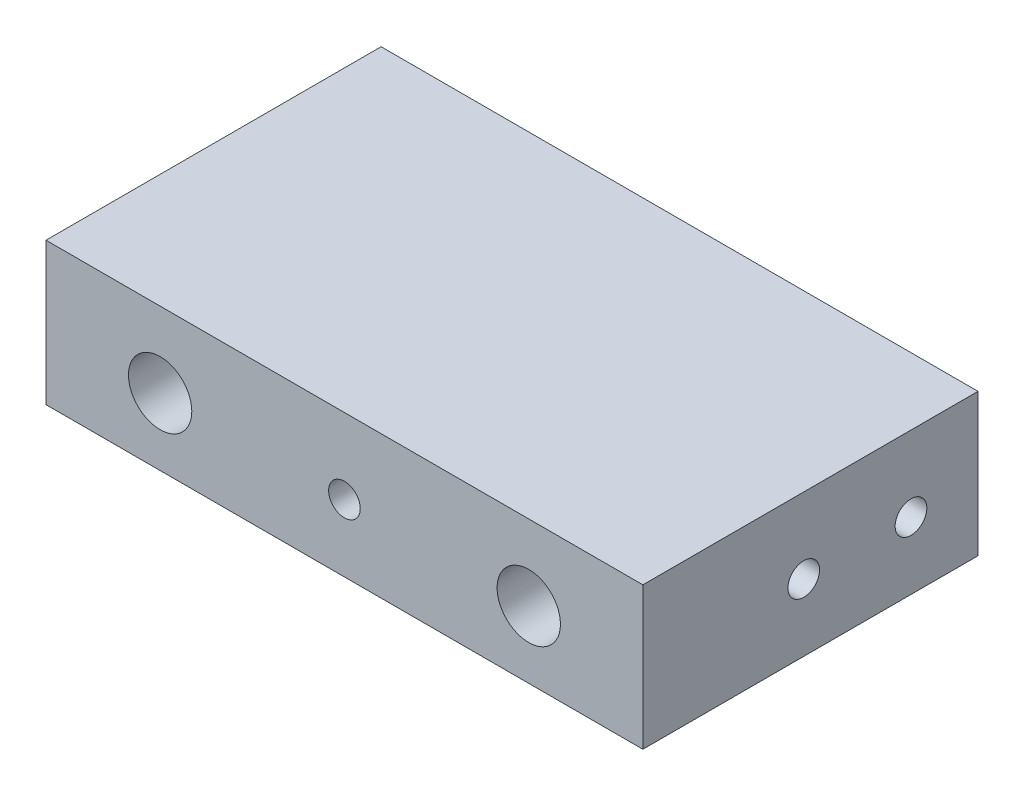
SolidWorks part; units mm, degrees
material "ABS"
ref_plane "X-Y Datum" through (0, 0, 0) normal (0, 0, 1) x (1, 0, 0)
ref_plane "X-Z Datum" through (0, 0, 0) normal (0, 1, 0) x (1, 0, 0)
ref_plane "Y-Z Datum" through (0, 0, 0) normal (1, 0, 0) x (0, 0, -1)
sketch "Sketch1" plane through (0, 0, 0) normal (0, 0, 1) x (1, 0, 0)
  line L1 (-28.275, 6.35) -> (28.275, 6.35)
  line L2 (-28.275, 6.35) -> (-28.275, -6.35)
  line L3 (-28.275, -6.35) -> (28.275, -6.35)
  line L4 (28.275, 6.35) -> (28.275, -6.35)
  line L5 (-28.275, 6.35) -> (28.275, -6.35) construction
  line L6 (-28.275, -6.35) -> (28.275, 6.35) construction
  point P0 (0, 0)
  dimension "D1" = 56.55
  dimension "D2" = 12.7
extrude "Boss-Extrude1" add sketch "Sketch1" along normal blind 31.75 contours L2 L3 L4 L1
sketch "Sketch2" plane through (0, 0, 31.75) normal (0, 0, 1) x (1, 0, 0)
  line L0 (-28.275, 0) -> (28.275, 0) construction
  line L1 (-28.275, 6.35) -> (-28.275, -6.35) construction
  line L2 (28.275, 6.35) -> (28.275, -6.35) construction
  line L3 (-17.4625, 0) -> (17.4625, 0) construction
  circle A0 centre (17.4625, 0) radius 3
  circle A1 centre (-17.4625, 0) radius 3
  circle A2 centre (0, 0) radius 1.5
  point P10 (0, 0)
  dimension "D1" = 6
  dimension "D3" = 3
  dimension "D2" = 34.925
extrude "Cut-Extrude1" cut sketch "Sketch2" against normal blind 10 contours A1 L0 L3 | L0 A1 L3 | L0 L3 A0 | L3 L0 A0 | A2 region at (17.4625, 0, 31.75) region at (-17.4625, 0, 31.75) region at (0, 0, 31.75)
sketch "Sketch3" plane through (-28.275, 0, 0) normal (-1, 0, 0) x (0, 0, 1)
  line L0 (31.75, 0) -> (0, 0) construction
  line L1 (31.75, 6.35) -> (31.75, -6.35) construction
  line L2 (0, 6.35) -> (0, -6.35) construction
  circle A0 centre (6.35, 0) radius 1.5
  circle A1 centre (16.51, 0) radius 1.5
  dimension "D1" = 3
  dimension "D2" = 10.16
  dimension "D3" = 6.35
extrude "Cut-Extrude2" cut sketch "Sketch3" against normal blind 10 contours A0 L0 | L0 A0 | A1 L0 | L0 A1 region at (-28.275, -0.6366, 16.51) region at (-28.275, 0.6366, 16.51) region at (-28.275, -0.6366, 6.35) region at (-28.275, 0.6366, 6.35)
sketch "Sketch4" plane through (0, 6.35, 0) normal (0, 1, 0) x (1, 0, 0)
  line L4 (28.275, 0) -> (-28.275, 0)
  line L5 (-28.275, 0) -> (-28.275, -31.75)
  line L6 (-28.275, -31.75) -> (28.275, -31.75)
  line L7 (28.275, -31.75) -> (28.275, 0)
  line L8 (28.275, 0) -> (-28.275, 0)
  line L9 (-28.275, 0) -> (-28.275, -31.75)
  line L10 (-28.275, -31.75) -> (28.275, -31.75)
  line L11 (28.275, -31.75) -> (28.275, 0)
  dimension "D1" = 0
extrude "Boss-Extrude2" add sketch "Sketch4" along normal blind 0.7937
mirror "Mirror1" about plane through (0, 0, 0) normal (1, 0, 0) of "Cut-Extrude2"
